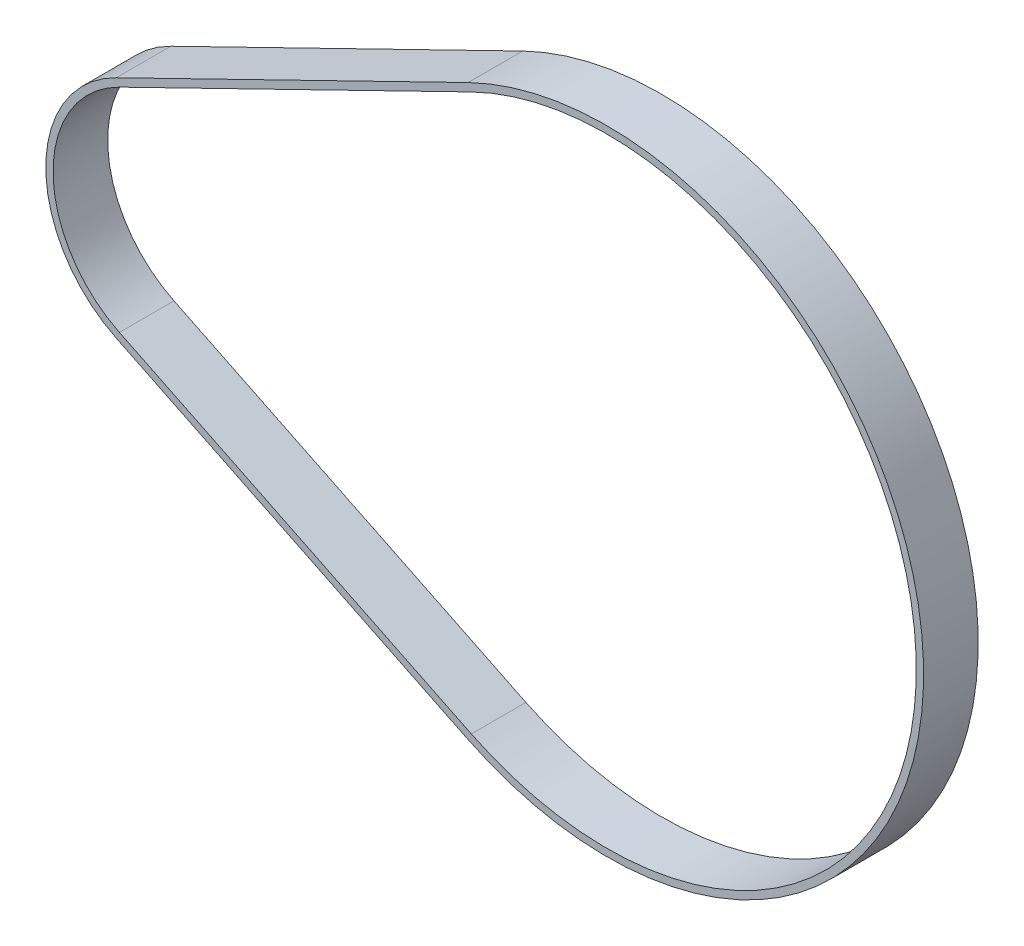
SolidWorks part; units mm, degrees
ref_plane "前视基准面" through (0, 0, 0) normal (0, 0, 1) x (1, 0, 0)
ref_plane "上视基准面" through (0, 0, 0) normal (0, 1, 0) x (1, 0, 0)
ref_plane "右视基准面" through (0, 0, 0) normal (1, 0, 0) x (0, 0, -1)
other "Configuration Table"
ref_plane "基准面1" through (0, 0, 0) normal (0, 0, 1) x (1, 0, 0)
sketch "草图1" plane through (0, 0, 0) normal (0, 0, 1) x (1, 0, 0)
  line L0 (-6.0485, -12.3905) -> (32.6254, -31.2696)
  line L1 (32.6254, 31.2696) -> (-6.0485, 12.3905)
  line L2 (-5.6976, -11.6716) -> (32.9764, -30.5507)
  line L3 (32.9764, 30.5507) -> (-5.6976, 11.6716)
  arc A0 (-6.0485, 12.3905) -> (-6.0485, -12.3905) centre (0, 0) ccw
  arc A1 (32.6254, -31.2696) -> (32.6254, 31.2696) centre (47.89, 0) ccw
  arc A2 (-5.6976, 11.6716) -> (-5.6976, -11.6716) centre (0, 0) ccw
  arc A3 (32.9764, -30.5507) -> (32.9764, 30.5507) centre (47.89, 0) ccw
extrude "凸台-拉伸1" add sketch "草图1" against normal blind 3 and the other way blind 3
